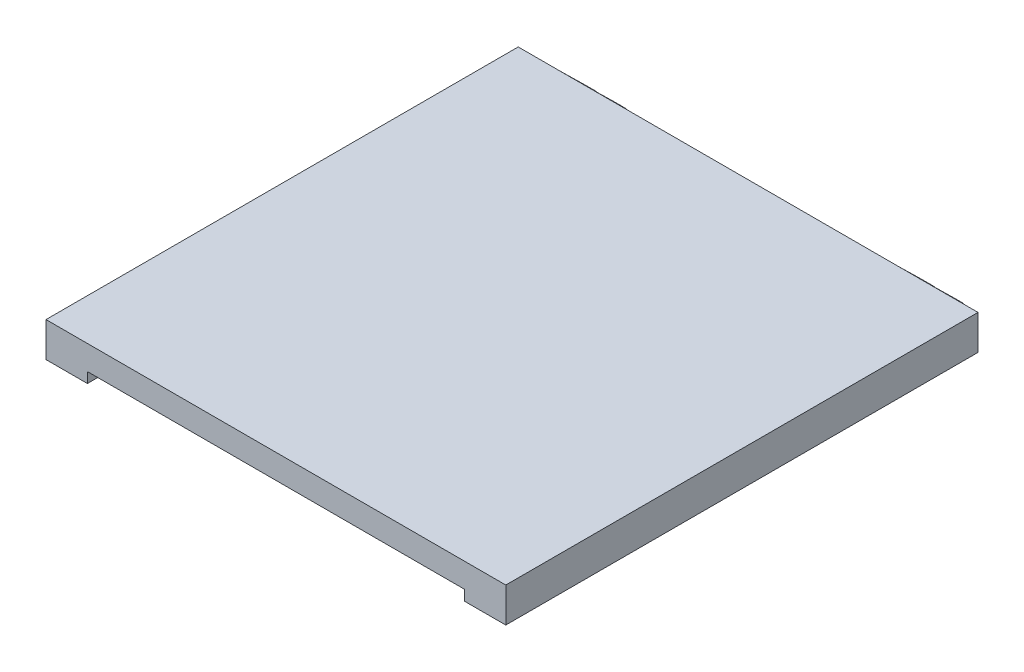
SolidWorks part; units mm, degrees
ref_plane "Front Plane" through (0, 0, 0) normal (0, 0, 1) x (1, 0, 0)
ref_plane "Top Plane" through (0, 0, 0) normal (0, 1, 0) x (1, 0, 0)
ref_plane "Right Plane" through (0, 0, 0) normal (1, 0, 0) x (0, 0, -1)
sketch "Sketch1" plane through (0, 0, 0) normal (0, 1, 0) x (1, 0, 0)
  line L1 (-70.485, -72.39) -> (70.485, -72.39)
  line L2 (-70.485, -72.39) -> (-70.485, 72.39)
  line L3 (-70.485, 72.39) -> (70.485, 72.39)
  line L4 (70.485, -72.39) -> (70.485, 72.39)
  line L5 (-70.485, -72.39) -> (70.485, 72.39) construction
  line L6 (-70.485, 72.39) -> (70.485, -72.39) construction
  point P0 (0, 0)
  dimension "D1" = 144.78
  dimension "D2" = 140.97
extrude "Boss-Extrude1" add sketch "Sketch1" along normal blind 5.08
sketch "Sketch2" plane through (0, 0, 0) normal (0, -1, 0) x (1, 0, 0)
  line L0 (-70.485, 72.39) -> (70.485, 72.39) construction
  line L1 (-57.785, 56.515) -> (57.785, 56.515)
  line L2 (-57.785, 56.515) -> (-57.785, 69.215)
  line L3 (-57.785, 69.215) -> (57.785, 69.215)
  line L4 (57.785, 56.515) -> (57.785, 69.215)
  line L5 (-57.785, 56.515) -> (57.785, 69.215) construction
  line L6 (-57.785, 69.215) -> (57.785, 56.515) construction
  line L7 (-70.485, -72.39) -> (-70.485, 72.39) construction
  line L8 (70.485, -72.39) -> (-70.485, -72.39) construction
  line L9 (70.485, 72.39) -> (70.485, -72.39) construction
  line L10 (-70.485, 72.39) -> (70.485, 72.39)
  line L11 (-70.485, -72.39) -> (-70.485, 72.39)
  line L12 (70.485, -72.39) -> (-70.485, -72.39)
  line L13 (70.485, 72.39) -> (70.485, -72.39)
  line L15 (-65.405, 53.34) -> (65.405, 53.34)
  line L16 (-65.405, 53.34) -> (-65.405, -67.31)
  line L17 (-65.405, -67.31) -> (65.405, -67.31)
  line L18 (65.405, 53.34) -> (65.405, -67.31)
  point P0 (0, 62.865)
  dimension "D1" = 5.08
  dimension "D2" = 5.08
  dimension "D3" = 12.7
  dimension "D4" = 5.08
  dimension "D5" = 3.175
  dimension "D6" = 12.7
  dimension "D7" = 12.7
  dimension "D8" = 3.175
extrude "Boss-Extrude2" add sketch "Sketch2" along normal blind 5.5562
sketch "Sketch3" plane through (0, -5.5562, 0) normal (0, -1, 0) x (1, 0, 0)
  line L0 (70.485, 72.39) -> (-70.485, 72.39) construction
  line L1 (-57.785, 72.39) -> (57.785, 72.39)
  line L2 (-57.785, 72.39) -> (-57.785, 53.34)
  line L3 (-57.785, 53.34) -> (57.785, 53.34)
  line L4 (57.785, 72.39) -> (57.785, 53.34)
  line L5 (65.405, 53.34) -> (-65.405, 53.34) construction
  line L6 (-57.785, 69.215) -> (-57.785, 56.515) construction
  line L7 (57.785, 56.515) -> (57.785, 69.215) construction
extrude "Cut-Extrude1" cut sketch "Sketch3" against normal blind 3.175
ref_plane "Plane1" through (57.785, 0, 0) normal (1, 0, 0) x (0, 0, -1)
sketch "Sketch4" plane through (57.785, 0, 0) normal (1, 0, 0) x (0, 0, -1)
  line L1 (79.4907, -2.0563) -> (75.4493, -2.0562) construction
  line L2 (75.4493, -2.0562) -> (73.4285, -5.5562) construction
  line L3 (73.4285, -5.5562) -> (75.4493, -9.0562) construction
  line L4 (75.4493, -9.0562) -> (79.4907, -9.0562) construction
  line L5 (79.4907, -9.0562) -> (81.5115, -5.5562) construction
  line L6 (81.5115, -5.5562) -> (79.4907, -2.0563) construction
  line L7 (72.39, 5.08) -> (72.39, -5.5562) construction
  line L8 (72.39, -5.5562) -> (-72.39, -5.5562) construction
  line L9 (72.39, 5.08) -> (80.2986, -2.6697)
  line L10 (74.2548, -8.0049) -> (72.39, -5.5562)
  line L11 (72.39, 5.08) -> (72.39, -5.5562)
  circle A0 centre (77.47, -5.5562) radius 4.0415 construction
  circle A1 centre (77.47, -5.5562) radius 2.2
  arc A2 (80.2986, -2.6697) -> (74.2548, -8.0049) centre (77.47, -5.5562) cw
  dimension "D3" = 4.4
  dimension "D1" = 7
  dimension "D2" = 5.08
extrude "Boss-Extrude3" add sketch "Sketch4" against normal blind 3
ref_plane "Plane2" through (51.785, 0, 0) normal (-1, 0, 0) x (0, 0, 1)
mirror "Mirror1" about plane through (51.785, 0, 0) normal (-1, 0, 0) of "Boss-Extrude3"
mirror "Mirror2" about plane through (0, 0, 0) normal (1, 0, 0) of "Boss-Extrude3", "Mirror1"
